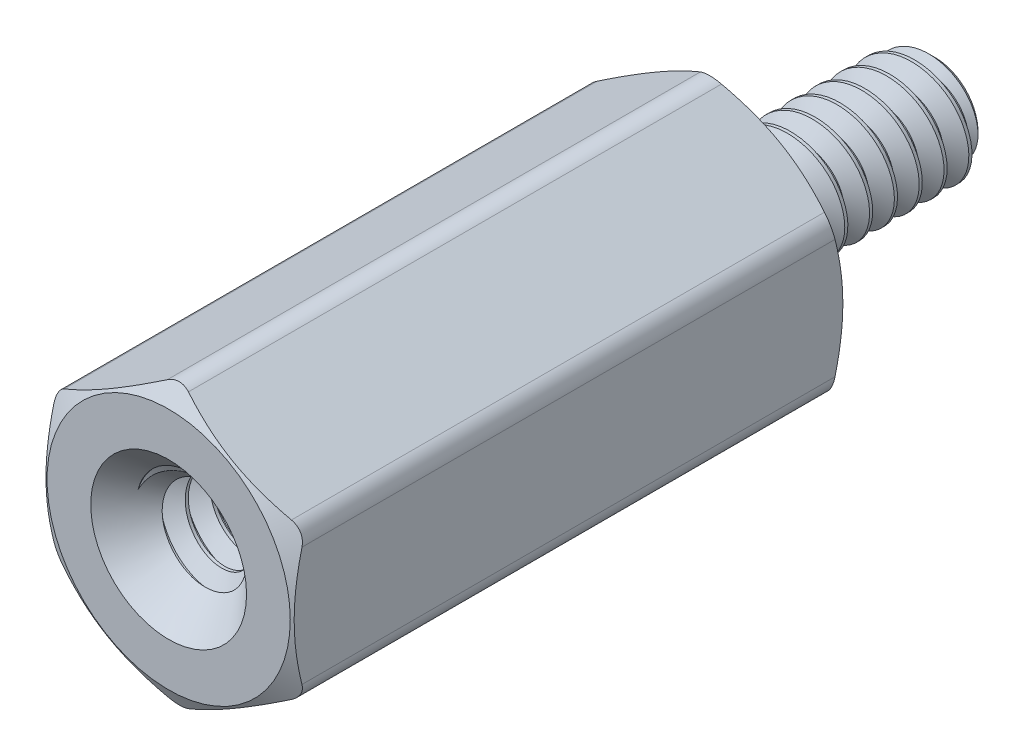
SolidWorks part; units mm, degrees
ref_plane "Front Plane" through (0, 0, 0) normal (0, 0, 1) x (1, 0, 0)
ref_plane "Top Plane" through (0, 0, 0) normal (0, 1, 0) x (1, 0, 0)
ref_plane "Right Plane" through (0, 0, 0) normal (1, 0, 0) x (0, 0, -1)
sketch "Sketch1" plane through (0, 0, 0) normal (0, 0, 1) x (1, 0, 0)
  line L1 (2.25, 1.299) -> (0, 2.5981)
  line L2 (0, 2.5981) -> (-2.25, 1.299)
  line L3 (-2.25, 1.299) -> (-2.25, -1.299)
  line L4 (-2.25, -1.299) -> (0, -2.5981)
  line L5 (0, -2.5981) -> (2.25, -1.299)
  line L6 (2.25, -1.299) -> (2.25, 1.299)
  circle A0 centre (0, 0) radius 2.25 construction
  point P10 (0, -2.25)
  dimension "Hex Size" = 4.5
sketch "Sketch2" plane through (0, 0, 0) normal (1, 0, 0) x (0, 0, -1)
  line L0 (3.9, 0) -> (-10, 0) construction
  line L2 (0, 1) -> (0, -1) construction
  line L3 (-5.2, 1) -> (-5.2, -1) construction
  line L4 (-10.4219, 1.0487) -> (-10.1969, 0.659) construction
  line L5 (-10.1969, 0.659) -> (-9.9719, 1.0487) construction
  line L6 (-9.9719, 1.0487) -> (-10.4219, 1.0487) construction
  line L7 (-10.3938, 1) -> (-10, 1) construction
  line L8 (-10.225, 0.7077) -> (-10.1688, 0.7077) construction
  line L9 (-10.1969, 0.7077) -> (-10.1969, 0.659) construction
  line L10 (-10.1969, 1) -> (-10.1969, 1.0487) construction
  line L11 (3.8719, 1.0487) -> (4.3219, 1.0487) construction
  line L12 (4.3219, 1.0487) -> (4.0969, 0.659) construction
  line L13 (4.0969, 0.659) -> (3.8719, 1.0487) construction
  line L14 (3.9, 1) -> (4.2937, 1) construction
  line L15 (4.0687, 0.7077) -> (4.125, 0.7077) construction
  line L16 (4.0969, 0.7077) -> (4.0969, 0.659) construction
  line L17 (4.0969, 1) -> (4.0969, 1.0487) construction
  line L18 (0, 2.5981) -> (-10, 2.5981) construction
  point P6 (0, 0)
  point P9 (-5.2, 0)
  dimension "Length" = 10
sketch "Sketch3" plane through (0, 0, 0) normal (1, 0, 0) x (0, 0, -1)
  line L0 (-5.2, 0) -> (3.9, 0)
  line L1 (-5.2, 1) -> (-5.2, -1) construction
  line L2 (3.9, 0) -> (3.9, 0.775)
  line L3 (3.9, 0.775) -> (3.675, 1)
  line L4 (3.675, 1) -> (0.6367, 1)
  line L5 (0.6367, 1) -> (0.468, 0.7077)
  line L6 (-5.2, 0) -> (-5.2, 0.775)
  line L7 (-5.2, 0.775) -> (-5.425, 1)
  line L8 (-5.425, 1) -> (-9.775, 1)
  line L9 (-9.775, 1) -> (-10, 1.225)
  line L10 (3.675, 0) -> (3.675, -1) construction
  line L11 (-10, 1.225) -> (-10, 2.25)
  line L12 (-10, 2.25) -> (0, 2.25)
  line L14 (0.468, 0.7077) -> (0.225, 0.7077)
  line L15 (0, 0.9327) -> (0, 2.25)
  arc A0 (0, 0.9327) -> (0.225, 0.7077) centre (0.225, 0.9327) ccw
  point P5 (-10, -2.25)
  point P8 (-8.875, -1)
  point P9 (2.775, -1)
  point P27 (0, 0.7077)
  dimension "D4" = 0.225
  dimension "D2" = 0.225
  dimension "D1" = 45
  dimension "D6" = 1.125
  dimension "D7" = 60
  dimension "D3" = 1.125
  dimension "D5" = 0.468
revolve "Revolve1" add sketch "Sketch3" angle 360 about L0 region at (0, 1.1531, 3.1945)
sketch "Sketch4" plane through (0, 0, 10) normal (0, 0, 1) x (1, 0, 0)
  line L0 (0, 2.25) -> (0, 1) construction
  line L1 (-2.25, 1.299) -> (-2.25, -1.299)
  line L2 (-2.25, -1.299) -> (0, -2.5981)
  line L3 (0, -2.5981) -> (2.25, -1.299)
  line L4 (2.25, -1.299) -> (2.25, 1.299)
  line L5 (2.25, 1.299) -> (0, 2.5981)
  line L6 (0, 2.5981) -> (-2.25, 1.299)
  circle A0 centre (0, 0) radius 2.25 construction
  circle A1 centre (0, 0) radius 1.625
  circle A2 centre (0, 0) radius 2.25 construction
  point P16 (0, 1.625)
extrude "Boss-Extrude1" add sketch "Sketch4" against normal up to surface (10 mm away) up to face at (0, 2.25, 0)
sketch "Sketch5" plane through (0, 0, 10) normal (0, 0, 1) x (1, 0, 0)
  line L0 (-0.5736, 0.8192) -> (0.5736, -0.8192) construction
  line L1 (0, 1) -> (0, -1) construction
  line L3 (0, -55) -> (0, 55) construction
  circle A0 centre (0, 0) radius 2.205
  point P11 (0.5736, -0.8192)
  dimension "D1" = 4.41
  dimension "D2" = 35
extrude "Cut-Extrude1" cut sketch "Sketch5" against normal through all draft 60 flip side to cut
sketch "Sketch6" plane through (0, 0, 0) normal (0, 0, -1) x (-1, 0, 0)
  circle A0 centre (0, 0) radius 2.205
  circle A1 centre (0, 0) radius 2.205 construction
extrude "Cut-Extrude2" cut sketch "Sketch6" against normal through all draft 60 flip side to cut
fillet "Fillet1" radius 0.3825 6 edges at (0, 2.5981, 5) (-2.25, -1.299, 5) (0, -2.5981, 5) (2.25, -1.299, 5) (2.25, 1.299, 5) (-2.25, 1.299, 5)
sketch "Drawing1" plane through (0, 0, 0) normal (1, 0, 0) x (0, 0, -1)
  line L0 (-10, 1) -> (-5.2, 1) construction
  line L1 (-5.2, 1) -> (-5.2, -1) construction
  line L2 (-5.2, -1) -> (-10, -1) construction
sketch "Sketch7" plane through (0, 0, 0) normal (-1, 0, 0) x (0, 0, 1)
  line L0 (-4.0687, 0.7077) -> (-4.125, 0.7077)
  line L1 (-4.125, 0.7077) -> (-4.3078, 1.0244)
  line L2 (-4.3219, 1.0487) -> (-4.0969, 0.659) construction
  line L3 (-4.3078, 1.0244) -> (-3.8859, 1.0244)
  line L4 (-4.0969, 0.659) -> (-3.8719, 1.0487) construction
  line L5 (-3.8859, 1.0244) -> (-4.0687, 0.7077)
  line L6 (-4.0969, 1) -> (-4.0969, 1.0487) construction
  point P12 (-4.0969, 1.0244)
sketch "Sketch8" plane through (0, 0, -3.9) normal (0, 0, -1) x (-1, 0, 0)
  circle A0 centre (0, 0) radius 1
curve "Helix/Spiral1" pitch 0.45 height 3.783 radius 1 centre (0, 0, -3.9) axis (0, 0, 1) start towards (0, 1, 0)
sweep "Cut-Sweep1" cut profiles "Sketch7" path "Helix/Spiral1" align with end faces yes
sketch "Sketch9" plane through (0, 0, 5.2) normal (0, 0, 1) x (1, 0, 0)
  circle A0 centre (0, 0) radius 1.225
extrude "Boss-Extrude2" add sketch "Sketch9" along normal up to surface (4.8 mm away) up to face at (0, 1.225, 10)
sketch "Sketch10" plane through (0, 0, 0) normal (1, 0, 0) x (0, 0, -1)
  line L0 (3.9, 0) -> (-10, 0) construction
  line L1 (-5.2, 1) -> (-10, 1)
  line L2 (-5.2, 1) -> (-5.2, 0)
  line L3 (-5.2, 0) -> (-10, 0)
  line L4 (-10, 1) -> (-10, 0)
revolve "Revolve2" add sketch "Sketch10" angle 360 about L0
sketch "Sketch11" plane through (0, 0, 10) normal (0, 0, 1) x (1, 0, 0)
  circle A0 centre (0, 0) radius 1
  circle A1 centre (0, 0) radius 1 construction
sketch "Sketch12" plane through (0, 0, 0) normal (1, 0, 0) x (0, 0, -1)
  line L0 (-10.225, 0.7077) -> (-10.1688, 0.7077)
  line L1 (-10.1688, 0.7077) -> (-9.9859, 1.0244)
  line L2 (-10.1969, 0.659) -> (-9.9719, 1.0487) construction
  line L3 (-9.9859, 1.0244) -> (-10.4078, 1.0244)
  line L4 (-10.4219, 1.0487) -> (-10.1969, 0.659) construction
  line L5 (-10.4078, 1.0244) -> (-10.225, 0.7077)
  line L6 (-10.1969, 1) -> (-10.1969, 1.0487) construction
  point P12 (-10.1969, 1.0244)
curve "Helix/Spiral2" pitch 0.45 height 5.25 radius 1 centre (0, 0, 10) axis (0, 0, -1) start towards (0, 1, 0)
sweep "Cut-Sweep2" cut profiles "Sketch12" path "Helix/Spiral2" align with end faces yes
combine bodies "Combine1" operation type subtract main body 113 bodies to subtract 114
sketch "Sketch13" plane through (0, 0, 10) normal (0, 0, 1) x (1, 0, 0)
  circle A0 centre (0, 0) radius 1.4125
  dimension "D1" = 2.825
extrude "Cut-Extrude3" cut sketch "Sketch13" against normal through all draft 45
equation "\"Thread Pitch (B)/8@Sketch2\" = \"Thread Pitch (B)@Sketch2\" / 8"
equation "\"Thread Pitch (A)/8@Sketch2\" = \"Thread Pitch (A)@Sketch2\" / 8"
equation "\"D1@Sketch5\"=\"Hex Size@Sketch1\" * .98"
equation "\"D1@Fillet1\"=\"Hex Size@Sketch1\" * .085"
equation "\"D2@Sketch3\"=\"Thread Pitch (A)@Sketch2\" * .5"
equation "\"D4@Sketch3\" = \"D2@Sketch3\""
equation "\"D6@Sketch3\" = \"Thread Pitch (A)@Sketch2\" * 2.5"
equation "\"D3@Helix/Spiral1\" = \"Thread Length (A)@Sketch2\" - \"D5@Sketch3\" * .25"
equation "\"D4@Helix/Spiral1\" = \"Thread Pitch (A)@Sketch2\""
equation "\"D3@Sketch3\" = \"Thread Pitch (B)@Sketch2\" * 2.5"
equation "\"D5@Sketch3\" = \"Thread Length (A)@Sketch2\" * .12"
equation "\"D3@Helix/Spiral2\" = \"Minimum Thread Length (B)@Sketch2\" + \"Thread Pitch (B)@Sketch2\""
equation "\"D4@Helix/Spiral2\" = \"Thread Pitch (B)@Sketch2\""
equation "\"D1@Sketch13\"=(\"Hex Size@Sketch1\"-\"Thread Size (A)@Sketch2\")*.33+\"Thread Size (A)@Sketch2\""
